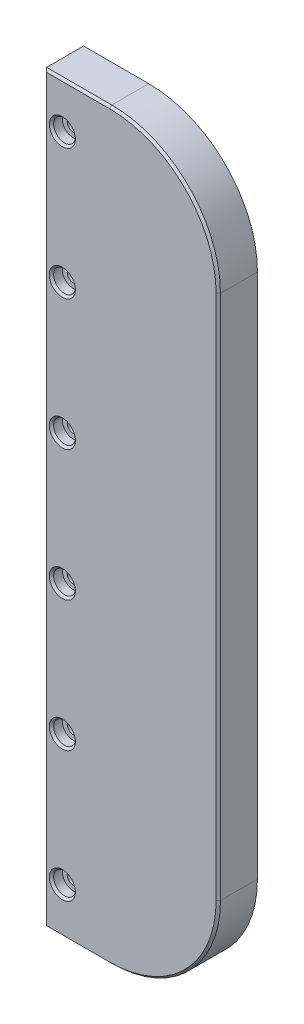
SolidWorks part; units mm, degrees
ref_plane "Front Plane" through (0, 0, 0) normal (0, 0, 1) x (1, 0, 0)
ref_plane "Top Plane" through (0, 0, 0) normal (0, 1, 0) x (1, 0, 0)
ref_plane "Right Plane" through (0, 0, 0) normal (1, 0, 0) x (0, 0, -1)
sketch "Sketch1" plane through (0, 0, 0) normal (0, 0, 1) x (1, 0, 0)
  line L1 (1, 271) -> (81, 271)
  line L2 (1, 271) -> (1, -71)
  line L3 (1, -71) -> (81, -71)
  line L4 (81, 271) -> (81, -71)
  dimension "D1" = 342
  dimension "D2" = 80
extrude "Boss-Extrude1" add sketch "Sketch1" along normal blind 18
fillet "Fillet1" radius 50 2 edges at (81, 271, 9) (81, -71, 9)
sketch "Sketch2" plane through (0, 0, 18) normal (0, 0, 1) x (1, 0, 0)
  circle A0 centre (9.25, -50) radius 2.5
  circle A1 centre (9.25, 10) radius 2.5
  circle A2 centre (9.25, 70) radius 2.5
  circle A3 centre (9.25, 130) radius 2.5
  circle A4 centre (9.25, 190) radius 2.5
  circle A5 centre (9.25, 250) radius 2.5
  point P0 (0, -80)
  dimension "D1" = 6
hole_wizard "CBORE for M5 SHCS1" positions "Sketch3" profile "Sketch4" counterbore size "M5" standard "ANSI Metric"
sketch "Sketch3" plane through (0, 0, 18) normal (0, 0, 1) x (1, 0, 0)
  point P0 (9.25, 250)
  point P3 (9.25, 190)
  point P6 (9.25, 130)
  point P9 (9.25, 70)
  point P12 (9.25, 10)
  point P15 (9.25, -50)
sketch "Sketch4" plane through (9.25, 250, 18) normal (1, 0, 0) x (0, -1, 0)
  line L0 (0, 0) -> (0, 30)
  line L1 (0, 30) -> (2.75, 28.3476)
  line L2 (2.75, 28.3476) -> (2.75, 5)
  line L3 (2.75, 5) -> (5, 5)
  line L4 (5, 5) -> (5, 0)
  line L5 (5, 0) -> (0, 0)
  line L10 (0, 30) -> (-2.75, 28.3476) construction
  line L11 (0, -6.35) -> (0, 107.95) construction
  dimension "Hole Dia." = 5.5
  dimension "Hole Depth" = 30
  dimension "C'Bore Dia." = 10
  dimension "C'Bore Depth" = 5
  dimension "Drill Angle" = 118
chamfer "Chamfer1" distance 1 angle 45 12 edges at (66.3553, -56.3553, 18) (16, -71, 18) (1, 100, 18) (16, 271, 18) (66.3553, 256.3553, 18) (81, 100, 18) (14.25, -50, 18) (14.25, 10, 18) (14.25, 70, 18) (14.25, 130, 18) (14.25, 190, 18) (14.25, 250, 18)
